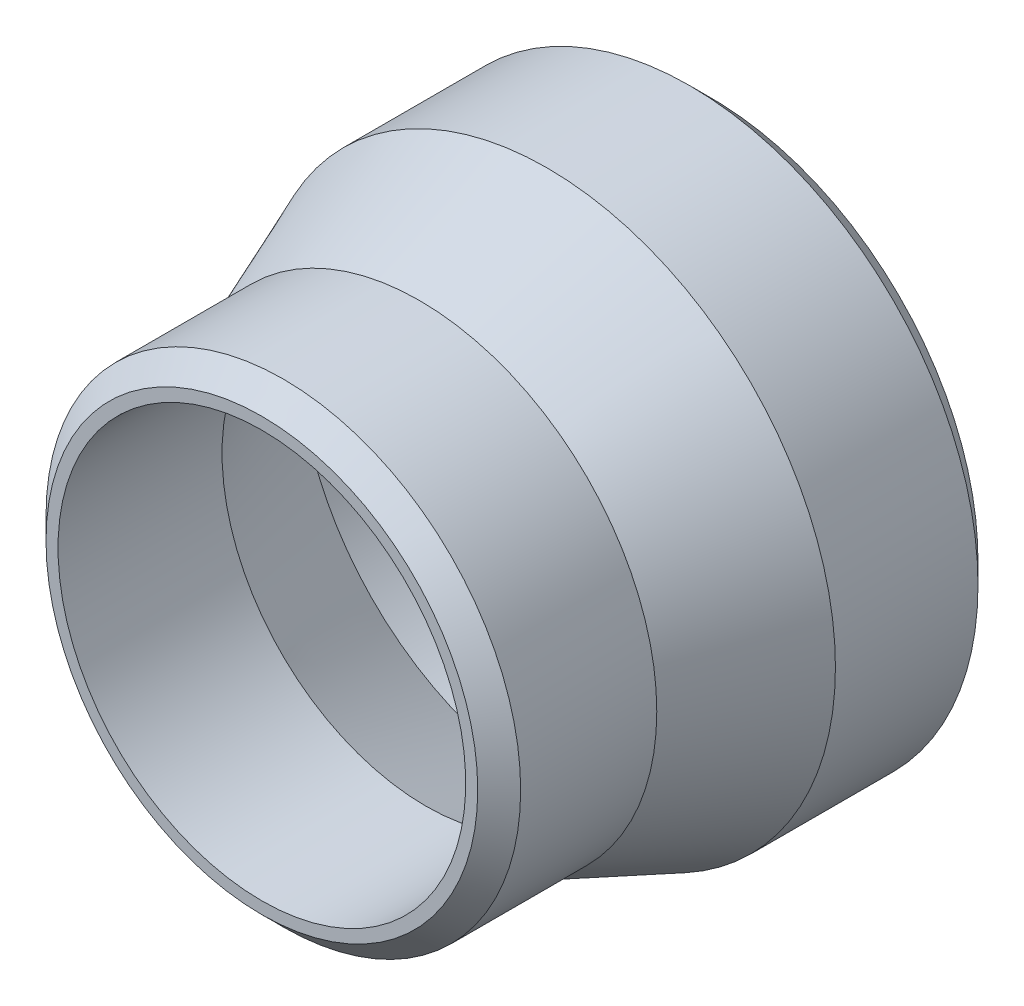
SolidWorks part; units mm, degrees
ref_plane "Pipe2 Plane" through (0, 0, 0) normal (0, 0, 1) x (1, 0, 0)
ref_plane "Top Plane" through (0, 0, 0) normal (0, 1, 0) x (1, 0, 0)
ref_plane "Right Plane" through (0, 0, 0) normal (1, 0, 0) x (0, 0, -1)
sketch "Sketch1" plane through (0, 0, 0) normal (1, 0, 0) x (0, 0, -1)
  line L0 (0, 0) -> (-53.1812, 0) construction
  line L1 (-53.1812, 0) -> (-53.1812, 28.0924) construction
  line L2 (-53.1812, 28.0924) -> (-34.5281, 28.0924)
  line L3 (-34.5281, 28.0924) -> (-19.4147, 34.1249)
  line L4 (-19.4147, 34.1249) -> (0, 34.1249)
  line L5 (0, 34.1249) -> (0, 0) construction
  line L6 (0, 34.1249) -> (0, 30.1625)
  line L7 (0, 30.1625) -> (-18.6531, 30.1625)
  line L8 (-18.6531, 30.1625) -> (-33.7665, 24.13)
  line L9 (-33.7665, 24.13) -> (-53.1812, 24.13)
  line L10 (-53.1812, 24.13) -> (-53.1812, 28.0924)
  line L11 (-34.5281, 28.0924) -> (-34.5281, 0) construction
  line L12 (-18.6531, 30.1625) -> (-18.6531, 0) construction
  line L13 (-34.5281, 14.0462) -> (-18.6531, 14.0462) construction
  line L14 (-26.5906, 14.0462) -> (-26.5906, 0) construction
  point P14 (-26.5906, 14.0462)
  point P15 (-26.5906, 0)
  dimension "H" = 53.1812
  dimension "WallThickness" = 3.9624
  dimension "PipeOD1" = 48.26
  dimension "D1" = 3.9624
  dimension "N" = 15.875
  dimension "PipeID2" = 60.325
revolve "Revolve1" add sketch "Sketch1" angle 360 about L0 region at (0, 29.1274, 26.5906)
chamfer "Chamfer1" distance 2.54 angle 45 2 edges at (0, 34.1249, 0) (0, 28.0924, 53.1812)
ref_plane "Pipe1 Plane" through (0, 0, 53.1812) normal (0, 0, 1) x (1, 0, 0)
other "CPoint1" parameters "Diameter"=38.1, "StubLength"=76.2
ref_axis "Axis1" through (0, 0, 63.1812) along (0, 0, -1)
other "CPoint2" parameters "Diameter"=50.8, "StubLength"=114.3
ref_axis "Axis2" through (0, 0, -10) along (0, 0, 1)
other "RPoint1"
equation "\"D1@Sketch1\"=\"WallThickness@Sketch1\""
